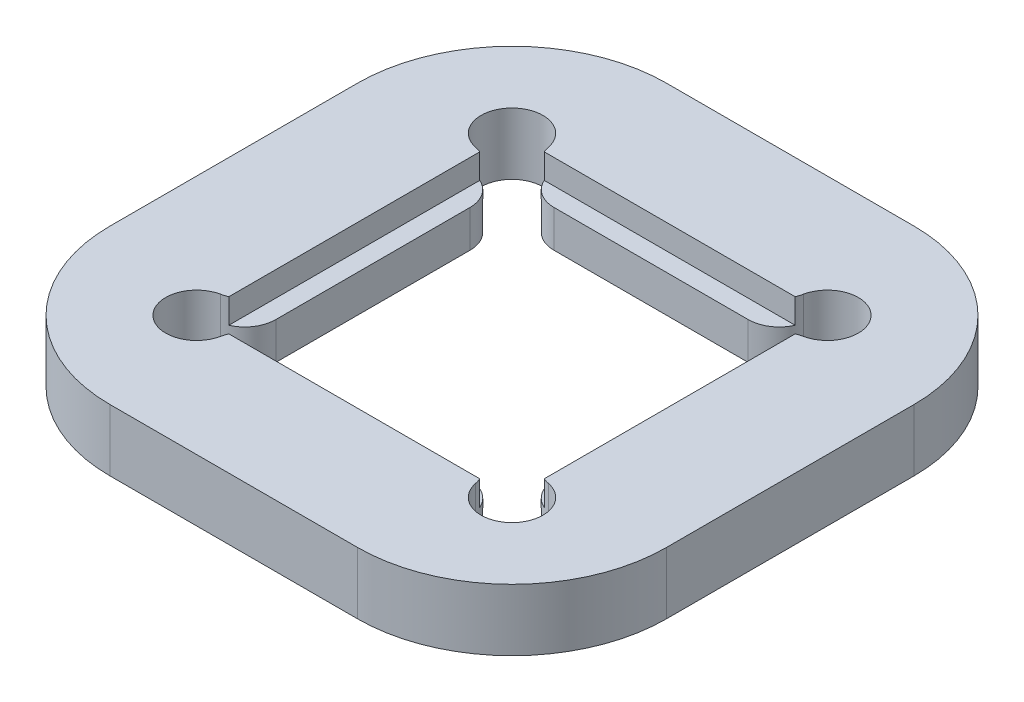
SolidWorks part; units mm, degrees
ref_plane "Alzado" through (0, 0, 0) normal (0, 0, 1) x (1, 0, 0)
ref_plane "Planta" through (0, 0, 0) normal (0, 1, 0) x (1, 0, 0)
ref_plane "Vista lateral" through (0, 0, 0) normal (1, 0, 0) x (0, 0, -1)
sketch "Croquis1" plane through (0, 0, 0) normal (0, 1, 0) x (1, 0, 0)
  line L1 (0, 0) -> (90, 0)
  line L2 (0, 0) -> (0, 90)
  line L3 (0, 90) -> (90, 90)
  line L4 (90, 0) -> (90, 90)
  dimension "D1" = 90
  dimension "D2" = 90
extrude "Saliente-Extruir1" add sketch "Croquis1" along normal blind 10
sketch "Croquis2" plane through (0, 10, 0) normal (0, 1, 0) x (1, 0, 0)
  line L0 (0, 90) -> (0, 0) construction
  line L1 (19.5, 70.5) -> (70.5, 70.5)
  line L2 (19.5, 70.5) -> (19.5, 19.5)
  line L3 (19.5, 19.5) -> (70.5, 19.5)
  line L4 (70.5, 70.5) -> (70.5, 19.5)
  line L6 (0, 0) -> (90, 0) construction
  dimension "D1" = 51
  dimension "D2" = 51
  dimension "D3" = 19.5
  dimension "D4" = 19.5
extrude "Cortar-Extruir1" cut sketch "Croquis2" against normal blind 4
sketch "Croquis3" plane through (0, 6, 0) normal (0, 1, 0) x (1, 0, 0)
  line L0 (19.5, 70.5) -> (19.5, 19.5) construction
  line L1 (22.5, 67.5) -> (67.5, 67.5)
  line L2 (22.5, 67.5) -> (22.5, 22.5)
  line L3 (22.5, 22.5) -> (67.5, 22.5)
  line L4 (67.5, 67.5) -> (67.5, 22.5)
  line L5 (70.5, 70.5) -> (19.5, 70.5) construction
  dimension "D1" = 45
  dimension "D2" = 45
  dimension "D3" = 3
  dimension "D4" = 3
extrude "Cortar-Extruir2" cut sketch "Croquis3" against normal through all
sketch "Croquis4" plane through (0, 10, 0) normal (0, 1, 0) x (1, 0, 0)
  circle A0 centre (19.5, 70.5) radius 5
  circle A1 centre (70.5, 70.5) radius 5
  circle A2 centre (19.5, 19.5) radius 5
  circle A3 centre (70.5, 19.5) radius 5
  dimension "D1" = 10
  dimension "D2" = 10
  dimension "D3" = 10
  dimension "D4" = 10
extrude "Cortar-Extruir3" cut sketch "Croquis4" against normal through all
fillet "Redondeo1" radius 5 8 edges at (23.5, 3, -67.5) (22.5, 3, -66.5) (67.5, 3, -66.5) (66.5, 3, -67.5) (22.5, 3, -23.5) (23.5, 3, -22.5) (66.5, 3, -22.5) (67.5, 3, -23.5)
fillet "Redondeo2" radius 25 4 edges at (90, 5, -90) (90, 5, 0) (0, 5, 0) (0, 5, -90)
ref_plane "Plano1" through (0, 5, 0) normal (0, 1, 0) x (1, 0, 0)
